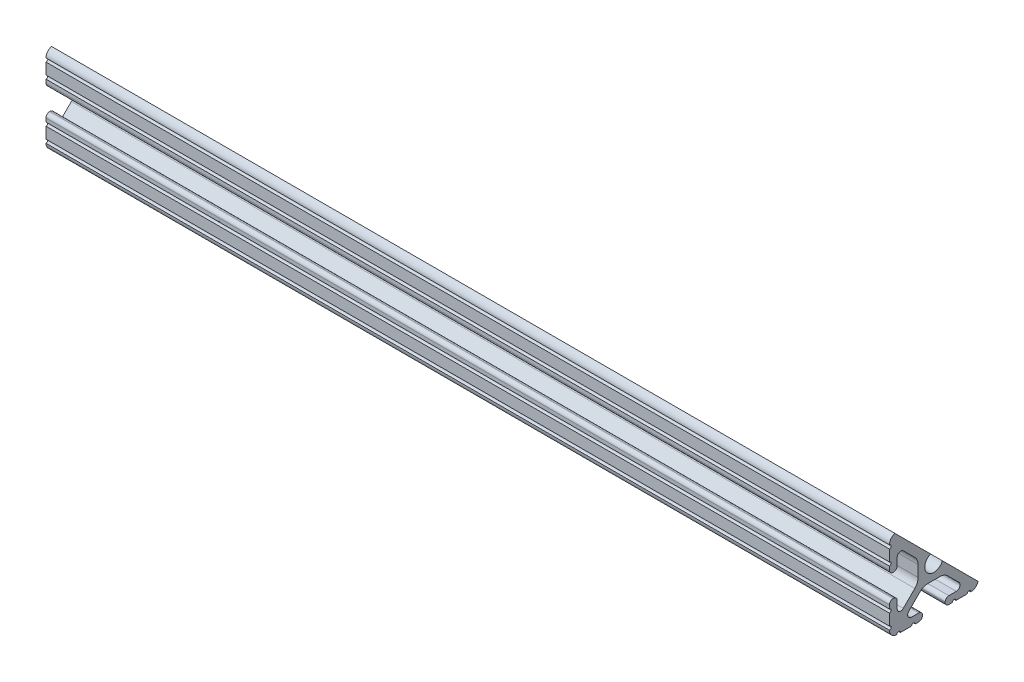
SolidWorks part; units mm, degrees
material "6061-T6 (SS)"
ref_plane "Front Plane" through (0, 0, 0) normal (0, 0, 1) x (1, 0, 0)
ref_plane "Top Plane" through (0, 0, 0) normal (0, 1, 0) x (1, 0, 0)
ref_plane "Right Plane" through (0, 0, 0) normal (1, 0, 0) x (0, 0, -1)
sketch "Sketch1" plane through (0, 0, 0) normal (1, 0, 0) x (0, 0, -1)
  line L0 (6.3331, -12.7) -> (9.5504, -12.7)
  line L1 (12.7, -9.5504) -> (12.7, -6.3331)
  line L2 (12.7, -5.3171) -> (12.7, -4.2875)
  line L3 (11.651, -3.2385) -> (11.5392, -3.2385)
  line L4 (10.4902, -4.2875) -> (10.4902, -6.4021)
  line L5 (8.7371, -7.1294) -> (5.441, -3.8408)
  line L6 (4.5085, -1.5932) -> (4.5085, 1.5932)
  line L7 (5.441, 3.8408) -> (8.7371, 7.1294)
  line L8 (10.4902, 6.4021) -> (10.4902, 4.2875)
  line L9 (11.5392, 3.2385) -> (11.651, 3.2385)
  line L10 (12.7, 4.2875) -> (12.7, 5.3171)
  line L11 (12.7, 6.3331) -> (12.7, 9.5504)
  line L12 (9.5504, 12.7) -> (6.3331, 12.7)
  line L13 (5.3171, 12.7) -> (4.2875, 12.7)
  line L14 (3.2385, 11.651) -> (3.2385, 11.5392)
  line L15 (4.2875, 10.4902) -> (6.4768, 10.4902)
  line L16 (7.207, 8.7244) -> (3.8983, 5.4232)
  line L17 (1.6558, 4.4958) -> (-1.6558, 4.4958)
  line L18 (-3.8983, 5.4232) -> (-7.207, 8.7244)
  line L19 (-6.4768, 10.4902) -> (-4.2875, 10.4902)
  line L20 (-3.2385, 11.5392) -> (-3.2385, 11.651)
  line L21 (-4.2875, 12.7) -> (-5.3171, 12.7)
  line L22 (-6.3331, 12.7) -> (-9.5504, 12.7)
  line L23 (-12.7, 9.5504) -> (-12.7, 6.3331)
  line L24 (-12.7, 5.3171) -> (-12.7, 4.2875)
  line L25 (-11.651, 3.2385) -> (-11.5392, 3.2385)
  line L26 (-10.4902, 4.2875) -> (-10.4902, 6.4021)
  line L27 (-8.7371, 7.1294) -> (-5.441, 3.8408)
  line L28 (-4.5085, 1.5932) -> (-4.5085, -1.5932)
  line L29 (-5.441, -3.8408) -> (-8.7371, -7.1294)
  line L30 (-10.4902, -6.4021) -> (-10.4902, -4.2875)
  line L31 (-11.5392, -3.2385) -> (-11.651, -3.2385)
  line L32 (-12.7, -4.2875) -> (-12.7, -5.3171)
  line L33 (-12.7, -6.3331) -> (-12.7, -9.5504)
  line L34 (-9.5504, -12.7) -> (-6.3331, -12.7)
  line L35 (-5.3171, -12.7) -> (-4.2875, -12.7)
  line L36 (-3.2385, -11.651) -> (-3.2385, -11.5392)
  line L37 (-4.2875, -10.4902) -> (-6.4164, -10.4902)
  line L38 (-7.1797, -8.6452) -> (-3.9523, -5.4237)
  line L39 (-1.7093, -4.4958) -> (1.7093, -4.4958)
  line L40 (3.9523, -5.4237) -> (7.1797, -8.6452)
  line L41 (6.4164, -10.4902) -> (4.2875, -10.4902)
  line L42 (3.2385, -11.5392) -> (3.2385, -11.651)
  line L43 (4.2875, -12.7) -> (5.3171, -12.7)
  circle A0 centre (0, 0) radius 2.6035
  arc A1 (6.3331, -12.7) -> (5.3171, -12.7) centre (5.8251, -12.7) ccw
  arc A2 (10.5664, -12.6998) -> (9.5504, -12.7) centre (10.0584, -12.7) ccw
  arc A3 (10.5664, -12.6998) -> (12.6998, -10.5664) centre (10.5918, -10.5918) ccw
  arc A4 (12.7, -9.5504) -> (12.6998, -10.5664) centre (12.7, -10.0584) ccw
  arc A5 (12.7, -5.3171) -> (12.7, -6.3331) centre (12.7, -5.8251) ccw
  arc A6 (12.7, -4.2875) -> (11.651, -3.2385) centre (11.651, -4.2875) ccw
  arc A7 (11.5392, -3.2385) -> (10.4902, -4.2875) centre (11.5392, -4.2875) ccw
  arc A8 (8.7371, -7.1294) -> (10.4902, -6.4021) centre (9.4628, -6.4021) ccw
  arc A9 (5.441, 3.8408) -> (4.5085, 1.5932) centre (7.6835, 1.5932) ccw
  arc A10 (10.4902, 6.4021) -> (8.7371, 7.1294) centre (9.4628, 6.4021) ccw
  arc A11 (10.4902, 4.2875) -> (11.5392, 3.2385) centre (11.5392, 4.2875) ccw
  arc A12 (11.651, 3.2385) -> (12.7, 4.2875) centre (11.651, 4.2875) ccw
  arc A13 (12.7, 6.3331) -> (12.7, 5.3171) centre (12.7, 5.8251) ccw
  arc A14 (12.6998, 10.5664) -> (12.7, 9.5504) centre (12.7, 10.0584) ccw
  arc A15 (12.6998, 10.5664) -> (10.5664, 12.6998) centre (10.5918, 10.5918) ccw
  arc A16 (9.5504, 12.7) -> (10.5664, 12.6998) centre (10.0584, 12.7) ccw
  arc A17 (5.3171, 12.7) -> (6.3331, 12.7) centre (5.8251, 12.7) ccw
  arc A18 (4.2875, 12.7) -> (3.2385, 11.651) centre (4.2875, 11.651) ccw
  arc A19 (3.2385, 11.5392) -> (4.2875, 10.4902) centre (4.2875, 11.5392) ccw
  arc A20 (7.207, 8.7244) -> (6.4768, 10.4902) centre (6.4768, 9.4563) ccw
  arc A21 (1.6558, 4.4958) -> (3.8983, 5.4232) centre (1.6558, 7.6708) ccw
  arc A22 (-3.8983, 5.4232) -> (-1.6558, 4.4958) centre (-1.6558, 7.6708) ccw
  arc A23 (-6.4768, 10.4902) -> (-7.207, 8.7244) centre (-6.4768, 9.4563) ccw
  arc A24 (-4.2875, 10.4902) -> (-3.2385, 11.5392) centre (-4.2875, 11.5392) ccw
  arc A25 (-3.2385, 11.651) -> (-4.2875, 12.7) centre (-4.2875, 11.651) ccw
  arc A26 (-6.3331, 12.7) -> (-5.3171, 12.7) centre (-5.8251, 12.7) ccw
  arc A27 (-10.5664, 12.6998) -> (-9.5504, 12.7) centre (-10.0584, 12.7) ccw
  arc A28 (-10.5664, 12.6998) -> (-12.6998, 10.5664) centre (-10.5918, 10.5918) ccw
  arc A29 (-12.7, 9.5504) -> (-12.6998, 10.5664) centre (-12.7, 10.0584) ccw
  arc A30 (-12.7, 5.3171) -> (-12.7, 6.3331) centre (-12.7, 5.8251) ccw
  arc A31 (-12.7, 4.2875) -> (-11.651, 3.2385) centre (-11.651, 4.2875) ccw
  arc A32 (-11.5392, 3.2385) -> (-10.4902, 4.2875) centre (-11.5392, 4.2875) ccw
  arc A33 (-8.7371, 7.1294) -> (-10.4902, 6.4021) centre (-9.4628, 6.4021) ccw
  arc A34 (-4.5085, 1.5932) -> (-5.441, 3.8408) centre (-7.6835, 1.5932) ccw
  arc A35 (-5.441, -3.8408) -> (-4.5085, -1.5932) centre (-7.6835, -1.5932) ccw
  arc A36 (-10.4902, -6.4021) -> (-8.7371, -7.1294) centre (-9.4628, -6.4021) ccw
  arc A37 (-10.4902, -4.2875) -> (-11.5392, -3.2385) centre (-11.5392, -4.2875) ccw
  arc A38 (-11.651, -3.2385) -> (-12.7, -4.2875) centre (-11.651, -4.2875) ccw
  arc A39 (-12.7, -6.3331) -> (-12.7, -5.3171) centre (-12.7, -5.8251) ccw
  arc A40 (-12.6998, -10.5664) -> (-12.7, -9.5504) centre (-12.7, -10.0584) ccw
  arc A41 (-12.6998, -10.5664) -> (-10.5664, -12.6998) centre (-10.5918, -10.5918) ccw
  arc A42 (-9.5504, -12.7) -> (-10.5664, -12.6998) centre (-10.0584, -12.7) ccw
  arc A43 (-5.3171, -12.7) -> (-6.3331, -12.7) centre (-5.8251, -12.7) ccw
  arc A44 (-4.2875, -12.7) -> (-3.2385, -11.651) centre (-4.2875, -11.651) ccw
  arc A45 (-3.2385, -11.5392) -> (-4.2875, -10.4902) centre (-4.2875, -11.5392) ccw
  arc A46 (-7.1797, -8.6452) -> (-6.4164, -10.4902) centre (-6.4164, -9.4098) ccw
  arc A47 (-1.7093, -4.4958) -> (-3.9523, -5.4237) centre (-1.7093, -7.6708) ccw
  arc A48 (3.9523, -5.4237) -> (1.7093, -4.4958) centre (1.7093, -7.6708) ccw
  arc A49 (6.4164, -10.4902) -> (7.1797, -8.6452) centre (6.4164, -9.4098) ccw
  arc A50 (4.2875, -10.4902) -> (3.2385, -11.5392) centre (4.2875, -11.5392) ccw
  arc A51 (3.2385, -11.651) -> (4.2875, -12.7) centre (4.2875, -11.651) ccw
  arc A52 (5.441, -3.8408) -> (4.5085, -1.5932) centre (7.6835, -1.5932) cw
  dimension "D1" = 3.175
extrude "Boss-Extrude1" add sketch "Sketch1" along normal blind 241.3
sketch "Sketch2" plane through (0, 0, 0) normal (-1, 0, 0) x (0, 0, 1)
  line L0 (-12.7, 12.7) -> (-12.7, -11.1827)
  line L1 (-12.7, -11.1827) -> (11.1827, 12.7)
  line L2 (11.1827, 12.7) -> (-12.7, 12.7)
  line L3 (-9.5504, 12.7) -> (-6.3331, 12.7) construction
  line L4 (-12.7, 6.3331) -> (-12.7, 9.5504) construction
  point P7 (-12.7, -14.1694)
  point P8 (-12.7, -11.1737)
extrude "Cut-Extrude1" cut sketch "Sketch2" against normal through all
